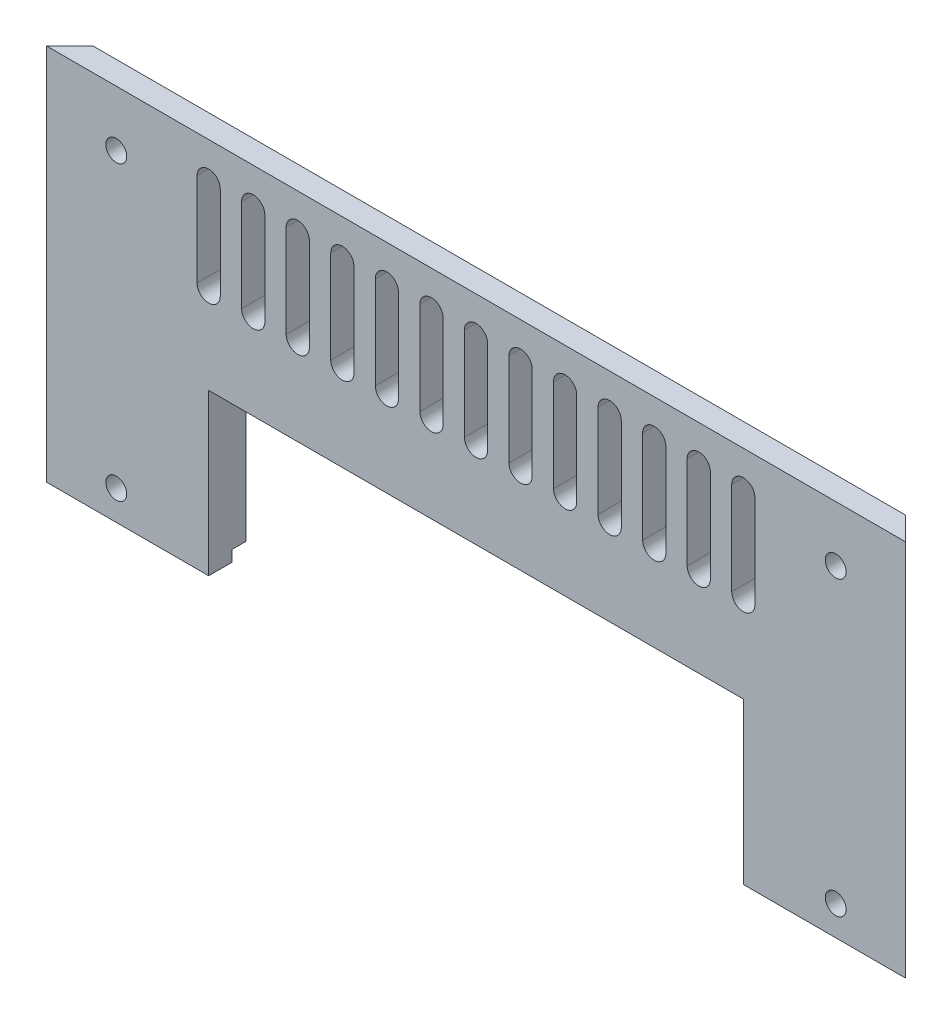
SolidWorks part; units mm, degrees
ref_plane "Front Plane" through (0, 0, 0) normal (0, 0, 1) x (1, 0, 0)
ref_plane "Top Plane" through (0, 0, 0) normal (0, 1, 0) x (1, 0, 0)
ref_plane "Right Plane" through (0, 0, 0) normal (1, 0, 0) x (0, 0, -1)
sketch "Sketch1" plane through (0, 0, 0) normal (0, 0, 1) x (1, 0, 0)
  line L0 (92.5, 84) -> (92.5, -37.3998) construction
  line L1 (0, 0) -> (185, 0)
  line L2 (0, 0) -> (0, 84)
  line L3 (0, 84) -> (185, 84)
  line L4 (185, 0) -> (185, 84)
  line L5 (0, 42) -> (185, 42) construction
  circle A0 centre (15, 9) radius 2.25
  circle A1 centre (170, 9) radius 2.25
  circle A4 centre (15, 72) radius 2.25
  circle A5 centre (170, 72) radius 2.25
  dimension "D3" = 15
  dimension "D5" = 4.5
  dimension "D1" = 84
  dimension "D2" = 185
  dimension "D4" = 9
  dimension "D6" = 2
  dimension "D7" = 12
extrude "Boss-Extrude1" add sketch "Sketch1" against normal blind 5
sketch "Sketch2" plane through (0, 0, -5) normal (0, 0, -1) x (-1, 0, 0)
  line L0 (0, 0) -> (-185, 0) construction
  line L1 (0, 0) -> (-185, 0) construction
  line L2 (0, 5) -> (-185, 5)
  line L3 (-185, 5) -> (-185, 84)
  line L4 (-185, 84) -> (0, 84)
  line L5 (0, 84) -> (0, 5)
  circle A1 centre (-15, 9) radius 2.25 construction
  circle A2 centre (-170, 9) radius 2.25 construction
  circle A5 centre (-15, 9) radius 2.25
  circle A6 centre (-170, 9) radius 2.25
  circle A8 centre (-15, 72) radius 2.25 construction
  circle A9 centre (-170, 72) radius 2.25 construction
  circle A10 centre (-15, 72) radius 2.25
  circle A11 centre (-170, 72) radius 2.25
  dimension "D1" = 5
extrude "Boss-Extrude2" add sketch "Sketch2" along normal blind 3
chamfer "Chamfer1" distance 8 angle 45 3 edges at (185, 44.5, -8) (0, 44.5, -8) (92.5, 84, -8)
chamfer "Chamfer3" distance 3 angle 45 1 edges at (92.5, 84, -8)
sketch "Sketch3" plane through (92.5, 0, -92.5) normal (0.7071, 0, -0.7071) x (-0.7071, 0, -0.7071)
  line L0 (-130.8148, 0) -> (-130.8148, 2.6)
  line L1 (-130.8148, 0) -> (-130.8148, 84) construction
  line L2 (-130.8148, 2.6) -> (-123.7437, 2.6)
  line L4 (-123.7437, 2.6) -> (-123.7437, 0)
  line L5 (-123.7437, 0) -> (-130.8148, 0)
  line L6 (-119.501, 5) -> (-123.7437, 5) construction
  dimension "D1" = 2.4
extrude "Cut-Extrude1" cut sketch "Sketch3" along direction (1, 0, 0) on the side against the normal through all
sketch "Sketch4" plane through (0, 0, 0) normal (0, 0, 1) x (1, 0, 0)
  line L0 (0, 2.6) -> (185, 2.6) construction
  line L1 (0, 2.6) -> (185, 2.6) construction
  line L2 (34.9, 2.6) -> (150.1, 2.6)
  line L4 (34.9, 2.6) -> (34.9, 37.2)
  line L5 (34.9, 37.2) -> (150.1, 37.2)
  line L6 (150.1, 2.6) -> (150.1, 37.2)
  line L7 (34.9, 76) -> (34.9, 56) construction
  line L8 (37.4, 76) -> (37.4, 56)
  line L9 (32.4, 76) -> (32.4, 56)
  line L10 (185, 84) -> (0, 84) construction
  line L11 (44.5, 76) -> (44.5, 56) construction
  line L12 (47, 76) -> (47, 56)
  line L13 (42, 76) -> (42, 56)
  line L14 (54.1, 76) -> (54.1, 56) construction
  line L15 (56.6, 76) -> (56.6, 56)
  line L16 (51.6, 76) -> (51.6, 56)
  line L17 (63.7, 76) -> (63.7, 56) construction
  line L18 (66.2, 76) -> (66.2, 56)
  line L19 (61.2, 76) -> (61.2, 56)
  line L20 (73.3, 76) -> (73.3, 56) construction
  line L21 (75.8, 76) -> (75.8, 56)
  line L22 (70.8, 76) -> (70.8, 56)
  line L23 (82.9, 76) -> (82.9, 56) construction
  line L24 (85.4, 76) -> (85.4, 56)
  line L25 (80.4, 76) -> (80.4, 56)
  line L26 (92.5, 76) -> (92.5, 56) construction
  line L27 (95, 76) -> (95, 56)
  line L28 (90, 76) -> (90, 56)
  line L29 (102.1, 76) -> (102.1, 56) construction
  line L30 (104.6, 76) -> (104.6, 56)
  line L31 (99.6, 76) -> (99.6, 56)
  line L32 (111.7, 76) -> (111.7, 56) construction
  line L33 (114.2, 76) -> (114.2, 56)
  line L34 (109.2, 76) -> (109.2, 56)
  line L35 (121.3, 76) -> (121.3, 56) construction
  line L36 (123.8, 76) -> (123.8, 56)
  line L37 (118.8, 76) -> (118.8, 56)
  line L38 (130.9, 76) -> (130.9, 56) construction
  line L39 (133.4, 76) -> (133.4, 56)
  line L40 (128.4, 76) -> (128.4, 56)
  line L41 (140.5, 76) -> (140.5, 56) construction
  line L42 (143, 76) -> (143, 56)
  line L43 (138, 76) -> (138, 56)
  line L44 (150.1, 76) -> (150.1, 56) construction
  line L45 (152.6, 76) -> (152.6, 56)
  line L46 (147.6, 76) -> (147.6, 56)
  arc A0 (37.4, 76) -> (32.4, 76) centre (34.9, 76) ccw
  arc A1 (32.4, 56) -> (37.4, 56) centre (34.9, 56) ccw
  arc A2 (47, 76) -> (42, 76) centre (44.5, 76) ccw
  arc A3 (42, 56) -> (47, 56) centre (44.5, 56) ccw
  arc A4 (56.6, 76) -> (51.6, 76) centre (54.1, 76) ccw
  arc A5 (51.6, 56) -> (56.6, 56) centre (54.1, 56) ccw
  arc A6 (66.2, 76) -> (61.2, 76) centre (63.7, 76) ccw
  arc A7 (61.2, 56) -> (66.2, 56) centre (63.7, 56) ccw
  arc A8 (75.8, 76) -> (70.8, 76) centre (73.3, 76) ccw
  arc A9 (70.8, 56) -> (75.8, 56) centre (73.3, 56) ccw
  arc A10 (85.4, 76) -> (80.4, 76) centre (82.9, 76) ccw
  arc A11 (80.4, 56) -> (85.4, 56) centre (82.9, 56) ccw
  arc A12 (95, 76) -> (90, 76) centre (92.5, 76) ccw
  arc A13 (90, 56) -> (95, 56) centre (92.5, 56) ccw
  arc A14 (104.6, 76) -> (99.6, 76) centre (102.1, 76) ccw
  arc A15 (99.6, 56) -> (104.6, 56) centre (102.1, 56) ccw
  arc A16 (114.2, 76) -> (109.2, 76) centre (111.7, 76) ccw
  arc A17 (109.2, 56) -> (114.2, 56) centre (111.7, 56) ccw
  arc A18 (123.8, 76) -> (118.8, 76) centre (121.3, 76) ccw
  arc A19 (118.8, 56) -> (123.8, 56) centre (121.3, 56) ccw
  arc A20 (133.4, 76) -> (128.4, 76) centre (130.9, 76) ccw
  arc A21 (128.4, 56) -> (133.4, 56) centre (130.9, 56) ccw
  arc A22 (143, 76) -> (138, 76) centre (140.5, 76) ccw
  arc A23 (138, 56) -> (143, 56) centre (140.5, 56) ccw
  arc A24 (152.6, 76) -> (147.6, 76) centre (150.1, 76) ccw
  arc A25 (147.6, 56) -> (152.6, 56) centre (150.1, 56) ccw
  point P2 (92.5, 2.6)
  point P9 (34.9, 66)
  point P20 (44.5, 66)
  point P27 (54.1, 66)
  point P34 (63.7, 66)
  point P41 (73.3, 66)
  point P48 (82.9, 66)
  point P55 (92.5, 66)
  point P62 (102.1, 66)
  point P69 (111.7, 66)
  point P76 (121.3, 66)
  point P83 (130.9, 66)
  point P90 (140.5, 66)
  point P97 (150.1, 66)
  dimension "D1" = 115.2
  dimension "D2" = 57.6
  dimension "D3" = 34.6
  dimension "D4" = 20
  dimension "D5" = 8
  dimension "D6" = 13
extrude "Cut-Extrude2" cut sketch "Sketch4" against normal through all contours L4 L5 L6 L2 | L9 A1 L8 A0 | L12 A3 L13 A2 | L15 A5 L16 A4 | L18 A7 L19 A6 | L21 A9 L22 A8 | L24 A11 L25 A10 | L27 A13 L28 A12 | L30 A15 L31 A14 | L33 A17 L34 A16 | L36 A19 L37 A18 | L39 A21 L40 A20 | L42 A23 L43 A22 | L45 A25 L46 A24
